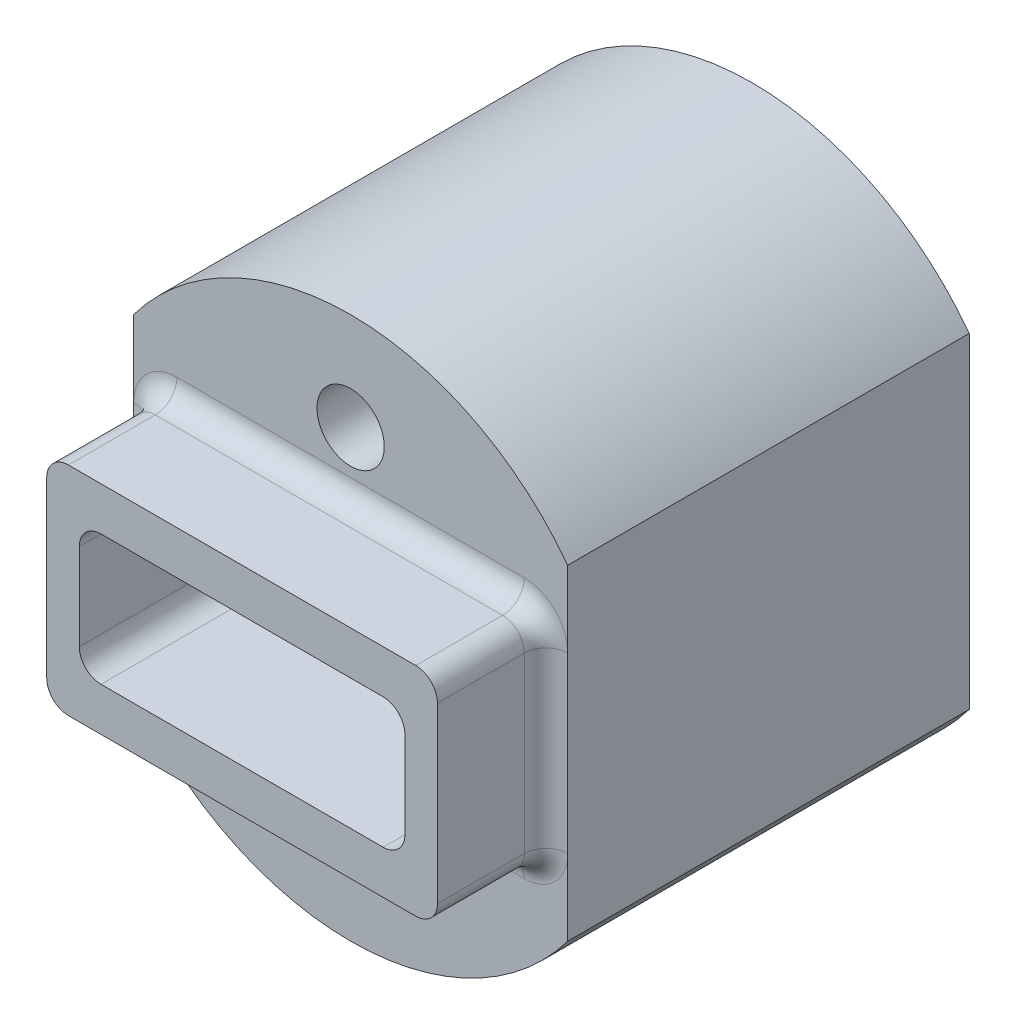
SolidWorks part; units mm, degrees
ref_plane "Ebene vorne" through (0, 0, 0) normal (0, 0, 1) x (1, 0, 0)
ref_plane "Ebene oben" through (0, 0, 0) normal (0, 1, 0) x (1, 0, 0)
ref_plane "Ebene rechts" through (0, 0, 0) normal (1, 0, 0) x (0, 0, -1)
sketch "Skizze1" plane through (0, 0, 0) normal (0, 0, 1) x (1, 0, 0)
  line L0 (0, 26.6232) -> (0, -18.9292) construction
  line L1 (-23.6459, 0) -> (19.5794, 0) construction
  circle A0 centre (0, 0) radius 12.5
  circle A1 centre (0, 8) radius 1.55
  circle A2 centre (0, -8) radius 1.55
  dimension "D1" = 25
  dimension "D2" = 3.1
  dimension "D3" = 16
extrude "Aufsatz-Linear austragen1" add sketch "Skizze1" along normal blind 7.5 and the other way blind 11
sketch "Skizze2" plane through (0, 0, -11) normal (0, 0, -1) x (-1, 0, 0)
  line L0 (-20.9915, 0) -> (20.1572, 0) construction
  line L1 (0, 18.5911) -> (0, -18.5544) construction
  line L2 (-9, -4) -> (-9, 4)
  line L3 (-8, 5) -> (8, 5)
  line L4 (-8, -5) -> (8, -5)
  line L5 (9, -4) -> (9, 4)
  arc A0 (-8, 5) -> (-9, 4) centre (-8, 4) ccw
  arc A1 (-8, -5) -> (-9, -4) centre (-8, -4) cw
  arc A2 (8, -5) -> (9, -4) centre (8, -4) ccw
  arc A3 (8, 5) -> (9, 4) centre (8, 4) cw
  point P13 (0, 5)
  point P14 (-9, 0)
  point P20 (9, 0)
  point P21 (0, -5)
  dimension "D1" = 1
  dimension "D2" = 10
  dimension "D3" = 18
extrude "Schnitt-Linear austragen1" cut sketch "Skizze2" against normal blind 4.5
sketch "Skizze3" plane through (0, 0, 7.5) normal (0, 0, 1) x (1, 0, 0)
  line L0 (18.7113, 0) -> (-15.5181, 0) construction
  line L1 (0, 15.8588) -> (0, -16.495) construction
  line L2 (-8, 5) -> (8, 5)
  line L3 (9, 4) -> (9, -4)
  line L4 (-8, -5) -> (8, -5)
  line L5 (-9, 4) -> (-9, -4)
  arc A0 (8, 5) -> (9, 4) centre (8, 4) cw
  arc A1 (8, -5) -> (9, -4) centre (8, -4) ccw
  arc A2 (-8, -5) -> (-9, -4) centre (-8, -4) cw
  arc A3 (-8, 5) -> (-9, 4) centre (-8, 4) ccw
  point P8 (0, 5)
  point P13 (9, 0)
  point P20 (-9, 0)
  point P21 (0, -5)
  dimension "D1" = 1
  dimension "D2" = 18
  dimension "D3" = 10
extrude "Aufsatz-Linear austragen2" add sketch "Skizze3" along normal blind 5
sketch "Skizze4" plane through (0, 0, 0) normal (0, 0, 1) x (1, 0, 0)
  line L0 (23.0396, 0) -> (-15.6217, 0) construction
  line L1 (0, -18.7774) -> (0, 16.1377) construction
  line L2 (-6.5, -3) -> (6.5, -3)
  line L3 (7.5, -2) -> (7.5, 2)
  line L4 (-7.5, -2) -> (-7.5, 2)
  line L5 (-6.5, 3) -> (6.5, 3)
  arc A0 (6.5, -3) -> (7.5, -2) centre (6.5, -2) ccw
  arc A1 (-6.5, -3) -> (-7.5, -2) centre (-6.5, -2) cw
  arc A2 (-6.5, 3) -> (-7.5, 2) centre (-6.5, 2) ccw
  arc A3 (6.5, 3) -> (7.5, 2) centre (6.5, 2) cw
  point P13 (7.5, 0)
  point P14 (0, -3)
  point P20 (0, 3)
  point P21 (-7.5, 0)
  dimension "D1" = 1
  dimension "D2" = 15
  dimension "D3" = 6
extrude "Schnitt-Linear austragen4" cut sketch "Skizze4" against normal through all and the other way through all
ref_axis "Achse1" through (0, 0, 13.475) along (0, 0, -1)
sketch "Skizze5" plane through (0, 0, 0) normal (0, 0, 1) x (1, 0, 0)
  line L0 (0, 18.6124) -> (0, -19.0354) construction
  line L1 (18.2952, 0) -> (-19.1412, 0) construction
  line L2 (10, 15) -> (10, -15)
  line L3 (10, 15) -> (-10, 15)
  line L4 (10, -15) -> (-10, -15)
  line L5 (-10, 15) -> (-10, -15)
  point P9 (10, 0)
  point P10 (-10, 0)
  point P12 (0, -15)
  point P13 (0, 15)
  dimension "D1" = 20
  dimension "D2" = 30
extrude "Schnitt-Linear austragen5" cut sketch "Skizze5" against normal through all and the other way blind 10 flip side to cut
fillet "Verrundung1" radius 1.2 8 edges at (-8.7071, 4.7071, -11) (-8.7071, -4.7071, -11) (0, -5, -11) (8.7071, -4.7071, -11) (8.7071, 4.7071, -11) (0, 5, -11) (-9, 0, -11) (9, 0, -11)
fillet "Verrundung2" radius 1 8 edges at (8.7071, 4.7071, 7.5) (9, 0, 7.5) (8.7071, -4.7071, 7.5) (0, -5, 7.5) (-8.7071, -4.7071, 7.5) (-9, 0, 7.5) (-8.7071, 4.7071, 7.5) (0, 5, 7.5)
